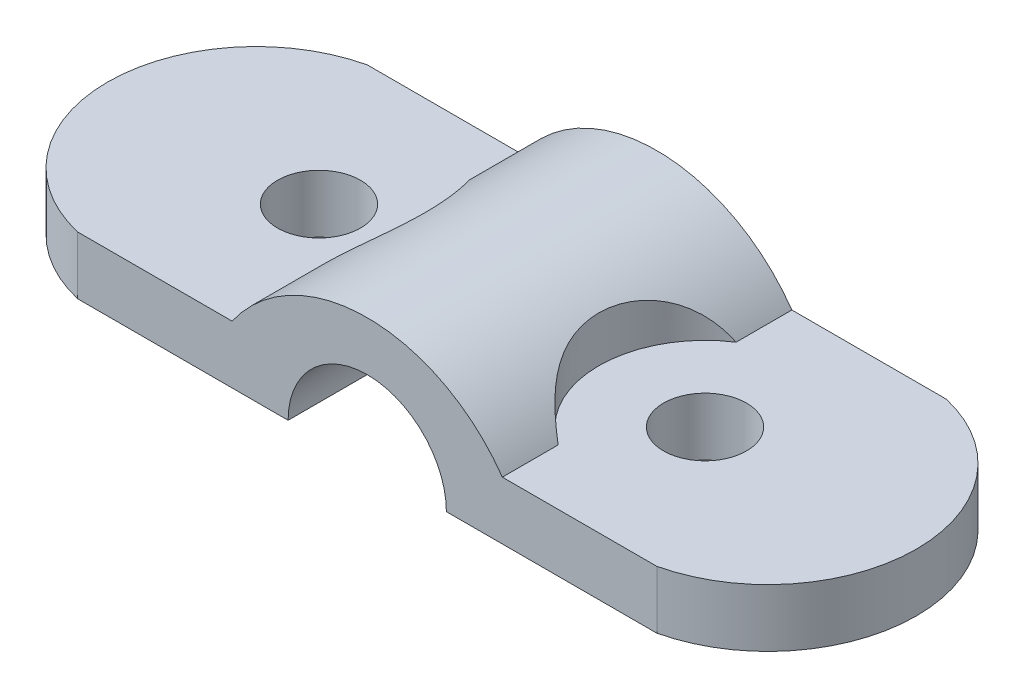
SolidWorks part; units mm, degrees
note: The reader was unsure of these and kept them because the rebuilt part matched: shared geometry of "Skizze3<8>", "Skizze3<9>".
material "ABS"
ref_plane "Ebene vorne" through (0, 0, 0) normal (0, 0, 1) x (1, 0, 0)
ref_plane "Ebene oben" through (0, 0, 0) normal (0, 1, 0) x (1, 0, 0)
ref_plane "Ebene rechts" through (0, 0, 0) normal (1, 0, 0) x (0, 0, -1)
sketch "Skizze2" plane through (0, 0, 0) normal (0, 0, 1) x (1, 0, 0)
  line L0 (0, 0) -> (10, 0)
  line L1 (10, 0) -> (15, 0)
  line L2 (0, 0) -> (-10, 0)
  line L3 (-10, 0) -> (-15, 0)
  line L4 (-15, 0) -> (-15, 3)
  line L5 (-15, 3) -> (-7, 3)
  line L6 (15, 0) -> (15, 3)
  line L7 (15, 3) -> (7, 3)
  arc A0 (4.1, 0) -> (-4.1, 0) centre (0, 0) ccw
  arc A1 (-7, 3) -> (7, 3) centre (0, -1.8703) cw
extrude "Aufsatz-Linear austragen1" add sketch "Skizze2" along normal blind 15 contours A1 L5 L4 L3 L2 A0 L0 L1 L6 L7
sketch "Skizze3" plane through (0, 3, 0) normal (0, 1, 0) x (1, 0, 0)
  line L0 (0, -7.5) -> (10, -7.5)
  line L3 (0, -7.5) -> (-10, -7.5)
  line L6 (-15, -7.5) -> (15, -7.5)
  line L7 (-15, -15) -> (-15, 0) construction
  line L8 (15, -15) -> (15, 0) construction
  line L9 (15, -15) -> (15, -7.5)
  line L10 (15, 0) -> (15, -7.5)
  line L11 (-15, -15) -> (-15, 0)
  arc A0 (15, -15) -> (15, 0) centre (13.2564, -7.5) ccw
  arc A1 (-15, -15) -> (-15, 0) centre (-13.2564, -7.5) cw
  circle A2 centre (10, -7.5) radius 2.15
  circle A3 centre (-10, -7.5) radius 2.15
  circle A4 centre (-10, -7.5) radius 5.5
  circle A5 centre (10, -7.5) radius 5.5
  dimension "D1" = 4.3
  dimension "D2" = 4.3
extrude "Aufsatz-Linear austragen2" add sketch "Skizze3" against normal blind 3
extrude "Schnitt-Linear austragen1" cut sketch "Skizze3<8>" along normal blind 3
sketch "Skizze3<8>" plane through (0, 3, 0) normal (0, 1, 0) x (1, 0, 0) same geometry as "Skizze3"
extrude "Schnitt-Linear austragen2" cut sketch "Skizze3<9>" against normal blind 3
sketch "Skizze3<9>" plane through (0, 3, 0) normal (0, 1, 0) x (1, 0, 0) same geometry as "Skizze3"
equation "\"M4_mutter\"= 7.4mm"
equation "\"M4_loch\"= 4.3mm"
equation "\"M8_loch\"= 8.4mm"
equation "\"D1@Skizze3\"=\"M4_loch\""
equation "\"D2@Skizze3\"=\"M4_loch\""
